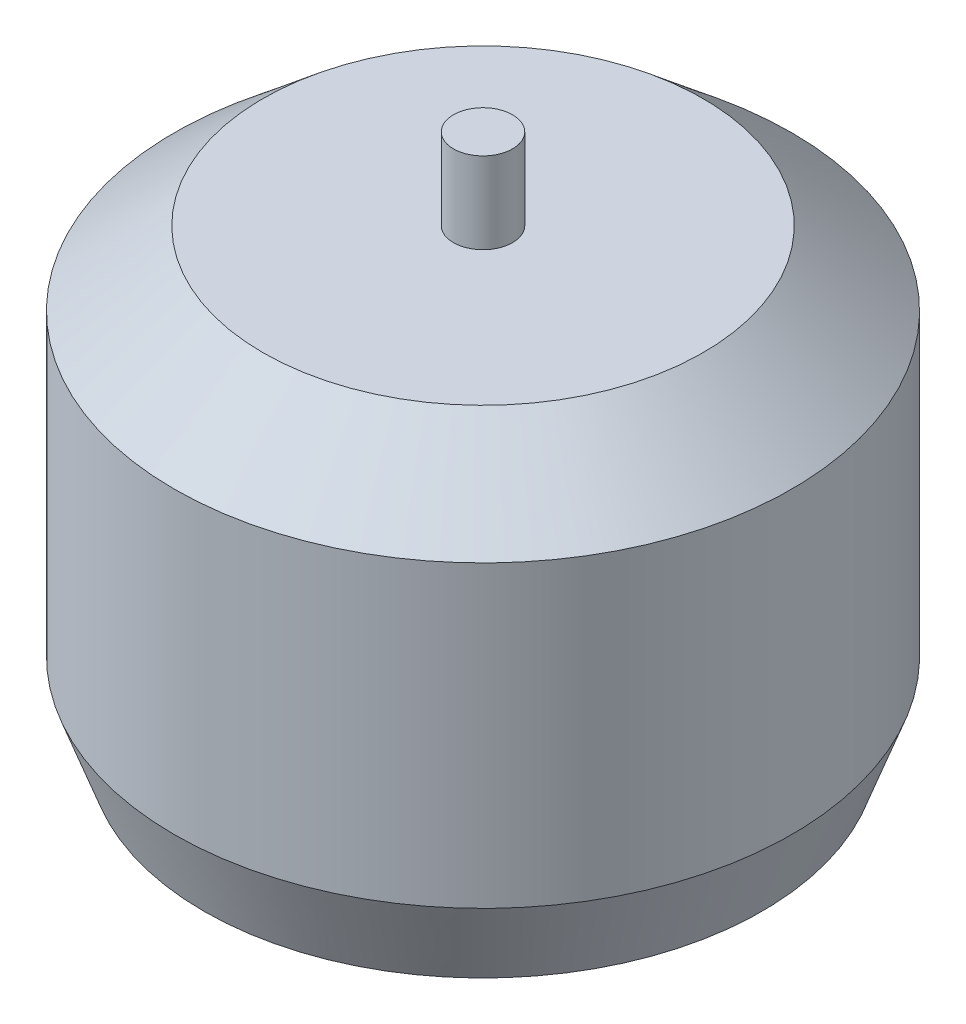
SolidWorks part; units mm, degrees
ref_plane "Front Plane" through (0, 0, 0) normal (0, 0, 1) x (1, 0, 0)
ref_plane "Top Plane" through (0, 0, 0) normal (0, 1, 0) x (1, 0, 0)
ref_plane "Right Plane" through (0, 0, 0) normal (1, 0, 0) x (0, 0, -1)
sketch "Sketch1" plane through (0, 0, 0) normal (0, 1, 0) x (1, 0, 0)
  circle A0 centre (-5.6491, -5.3281) radius 20.9
  dimension "D1" = 41.8
extrude "Boss-Extrude1" add sketch "Sketch1" along normal blind 30.75
chamfer "Chamfer1" distance 5 distance2 6 1 edges at (-5.6491, 30.75, 26.2281) first distance on face at (-5.6491, 30.75, 26.2281)
chamfer "Chamfer2" distance 2 angle 70 1 edges at (-5.6491, 0, 26.2281) first distance on face at (-5.6491, 0, 26.2281)
sketch "Sketch2" plane through (0, 30.75, 0) normal (0, 1, 0) x (1, 0, 0)
  circle A0 centre (-5.6491, -5.3281) radius 2
  circle A1 centre (-5.6491, -5.3281) radius 14.9 construction
  dimension "D1" = 4
  dimension "D2" = 0
  dimension "D3" = 0
extrude "Boss-Extrude2" add sketch "Sketch2" along normal blind 5.5
sketch "Sketch3" plane through (0, 0, 0) normal (0, -1, 0) x (1, 0, 0)
  circle A0 centre (-5.6491, 5.3281) radius 4
  circle A1 centre (-5.6491, 5.3281) radius 18.9 construction
  dimension "D1" = 8
  dimension "D2" = 0
extrude "Boss-Extrude3" add sketch "Sketch3" along normal blind 2.55 contours A0
sketch "Sketch4" plane through (0, 0, 0) normal (0, -1, 0) x (1, 0, 0)
  line L1 (19.434, 5.3281) -> (-5.6491, 5.3281) construction
  circle A0 centre (-5.9087, 17.486) radius 4
  circle A1 centre (-5.9087, -6.8299) radius 4
  circle A2 centre (-17.807, 5.5877) radius 4
  circle A3 centre (5.9897, 5.5877) radius 4
  circle A4 centre (-12.3666, 12.0456) radius 1
  circle A5 centre (1.0685, -1.3894) radius 1
  circle A6 centre (-11.3059, -0.3288) radius 1
  circle A7 centre (0.0078, 10.9849) radius 1
  circle A8 centre (-14.4879, -3.5107) radius 1
  circle A9 centre (3.1898, 14.1669) radius 1
  point P25 (-13.6764, -2.6993)
  dimension "D1" = 8
  dimension "D2" = 2
  dimension "D4" = 2
  dimension "D3" = 9.5
  dimension "D5" = 8
  dimension "D6" = 12.5
extrude "Cut-Extrude1" cut sketch "Sketch4" against normal blind 1.5875
